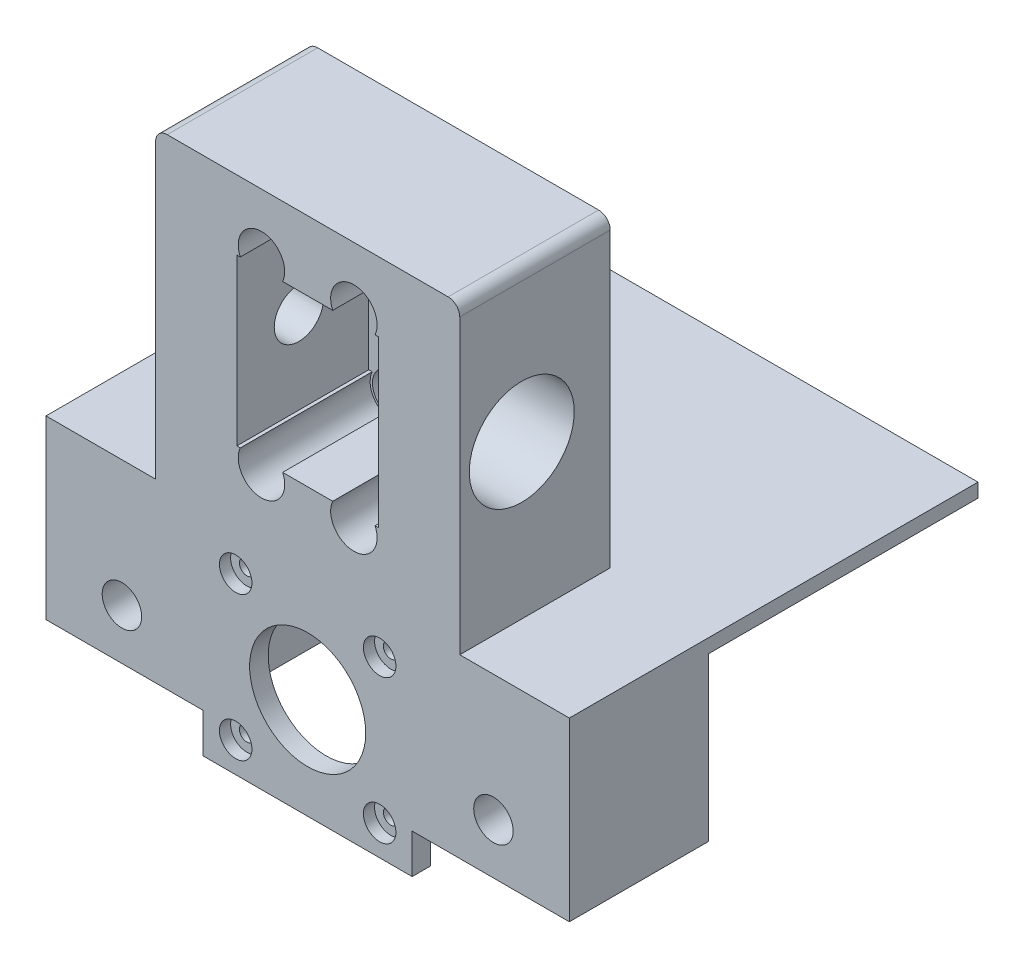
SolidWorks part; units mm, degrees
ref_plane "Front Plane" through (0, 0, 0) normal (0, 0, 1) x (1, 0, 0)
ref_plane "Top Plane" through (0, 0, 0) normal (0, 1, 0) x (1, 0, 0)
ref_plane "Right Plane" through (0, 0, 0) normal (1, 0, 0) x (0, 0, -1)
sketch "Sketch1" plane through (0, 0, 0) normal (0, 0, 1) x (1, 0, 0)
  line L1 (0, 0) -> (-65.5, 0)
  line L2 (0, 0) -> (0, -65.5)
  line L3 (0, -65.5) -> (-65.5, -65.5)
  line L4 (-65.5, 0) -> (-65.5, -65.5)
  line L5 (-17.5, -14.95) -> (-48, -14.95)
  line L6 (-17.5, -14.95) -> (-17.5, -50.55)
  line L7 (-17.5, -50.55) -> (-48, -50.55)
  line L8 (-48, -14.95) -> (-48, -50.55)
  point P10 (-32.75, -14.95)
  point P11 (-48, -32.75)
  point P12 (-65.5, -32.75)
  point P13 (-32.75, 0)
  dimension "D1" = 65.5
  dimension "D2" = 35.6
  dimension "D3" = 30.5
extrude "Boss-Extrude1" add sketch "Sketch1" along normal blind 28.4 and the other way blind 4
sketch "Sketch5" plane through (0, 0, 0) normal (1, 0, 0) x (0, 0, -1)
  line L2 (4, -65.5) -> (4, 0) construction
  line L4 (4, 0) -> (-28.4, 0) construction
  circle A1 centre (-15.05, -32.45) radius 11.3
  dimension "D1" = 11.3
  dimension "D2" = 19.05
  dimension "D3" = 32.45
extrude "Cut-Extrude1" cut sketch "Sketch5" against normal up to next
sketch "Sketch7" plane through (-65.5, 0, 0) normal (1, 0, 0) x (0, 0, -1)
  circle A1 centre (-15.05, -32.45) radius 5.3
  circle A3 centre (-15.05, -32.45) radius 11.3 construction
  circle A4 centre (-15.05, -32.45) radius 11.3 construction
  dimension "D1" = 5.3
extrude "Cut-Extrude4" cut sketch "Sketch7" along normal up to next
sketch "Sketch8" plane through (0, 0, -4) normal (0, 0, -1) x (-1, 0, 0)
  line L4 (17.5, -14.95) -> (17.5, -50.55)
  line L5 (48, -14.95) -> (17.5, -14.95)
  line L6 (48, -50.55) -> (48, -14.95)
  line L7 (17.5, -50.55) -> (48, -50.55)
  line L8 (17.5, -14.95) -> (17.5, -50.55)
  line L9 (48, -14.95) -> (17.5, -14.95)
  line L10 (48, -50.55) -> (48, -14.95)
  line L11 (17.5, -50.55) -> (48, -50.55)
  dimension "D2" = 30.5
  dimension "D3" = 35.6
  dimension "D1" = 0
extrude "Boss-Extrude2" add sketch "Sketch8" against normal blind 4
sketch "Sketch9" plane through (0, 0, -4) normal (0, 0, 1) x (1, 0, 0)
  line L0 (0, 0) -> (-65.5, 0) construction
  line L1 (0, 0) -> (0, -65.5) construction
  line L2 (0, -65.5) -> (-65.5, -65.5) construction
  line L3 (-32.75, -65.5) -> (-32.75, 0) construction
  line L4 (0, -32.75) -> (-65.5, -32.75) construction
  line L5 (-65.5, 0) -> (-65.5, -65.5) construction
  line L6 (-32.75, -65.5) -> (-32.75, -53.5) construction
  line L7 (-65.5, -65.5) -> (0, 0) construction
  circle A0 centre (-12.75, -12.9) radius 4.9
  circle A1 centre (-52.75, -12.9) radius 4.9
  circle A2 centre (-52.75, -52.6) radius 4.9
  circle A3 centre (-12.75, -52.6) radius 4.9
  point P20 (-32.75, -12)
  point P26 (-12, -32.75)
  point P27 (-53.5, -32.75)
  dimension "D3" = 9.8
  dimension "D1" = 12.9
  dimension "D2" = 12.75
  dimension "D4" = 12
extrude "Cut-Extrude5" cut sketch "Sketch9" along normal blind 2.2
fillet "Fillet1" radius 2.5 2 edges at (0, 0, 12.2) (-65.5, 0, 12.2)
sketch "Sketch10" plane through (0, 0, 0) normal (0, 0, 1) x (1, 0, 0)
  line L0 (0, -52.6) -> (-22.8, -52.6) construction
  line L1 (0, 0) -> (0, -65.5) construction
  line L2 (-22.8, -52.6) -> (-22.8, -65.5) construction
  line L3 (0, -65.5) -> (-65.5, -65.5) construction
  line L5 (-32.75, -65.5) -> (-32.75, 0) construction
  line L6 (0, -32.75) -> (-65.5, -32.75) construction
  line L7 (-32.75, -65.5) -> (-32.75, 0) construction
  line L8 (0, -32.75) -> (-65.5, -32.75) construction
  circle A0 centre (-22.8, -12.9) radius 5
  circle A1 centre (-42.7, -12.9) radius 5
  circle A2 centre (-22.8, -52.6) radius 5
  circle A3 centre (-42.7, -52.6) radius 5
  point P7 (-22.8, -12.9)
  point P8 (-42.7, -12.9)
  point P13 (-42.7, -52.6)
  dimension "D3" = 10
  dimension "D1" = 22.8
  dimension "D2" = 12.9
extrude "Cut-Extrude7" cut sketch "Sketch10" along normal up to next
sketch "Sketch20" plane through (0, 0, 0) normal (0, 0, 1) x (1, 0, 0)
  line L0 (-32.75, 0) -> (-32.75, -65.5) construction
  line L1 (-32.75, -65.5) -> (-32.75, 0) construction
  line L2 (-65.5, -32.75) -> (0, -32.75) construction
  line L3 (0, -32.75) -> (-65.5, -32.75) construction
  line L4 (-62.12, -65.5) -> (-3.38, -65.5) construction
  line L5 (0, -65.5) -> (-65.5, -65.5) construction
  line L6 (0, 0) -> (-65.5, 0) construction
  line L7 (0, 0) -> (0, -65.5) construction
  line L8 (-65.5, 0) -> (-65.5, -65.5) construction
  arc A0 (-38.1396, -14.95) -> (-47.2604, -14.95) centre (-42.7, -12.9) ccw construction
  point P0 (-42.7, -12.9)
  point P13 (-22.8, -12.9)
  point P15 (-22.8, -52.6)
  point P16 (-42.7, -52.6)
hole_wizard "CBORE for M4 Pan Head Machine Screw1" positions "3DSketch5" profile "Sketch22" counterbore size "M4" standard "ANSI Metric"
sketch3d "3DSketch5"
  point P0 (-42.7, -12.9, 0)
  point P3 (-22.8, -12.9, 0)
  point P6 (-42.7, -52.6, 0)
  point P9 (-22.8, -52.6, 0)
sketch "Sketch22" plane through (-42.7, -12.9, 0) normal (1, 0, 0) x (0, -1, 0)
  line L0 (0, 0) -> (0, 9.4421)
  line L1 (0, 9.4421) -> (2.4, 8)
  line L2 (2.4, 8) -> (2.4, 3.1)
  line L3 (2.4, 3.1) -> (4.5, 3.1)
  line L4 (4.5, 3.1) -> (4.5, 0)
  line L5 (4.5, 0) -> (0, 0)
  line L10 (0, 9.4421) -> (-2.4, 8) construction
  line L11 (0, -6.35) -> (0, 107.95) construction
  dimension "Hole Dia." = 4.8
  dimension "Hole Depth" = 8
  dimension "C'Bore Dia." = 9
  dimension "C'Bore Depth" = 3.1
  dimension "Drill Angle" = 118
sketch "Sketch23" plane through (0, -65.5, 0) normal (0, -1, 0) x (1, 0, 0)
  line L1 (23.6, 28.4) -> (-89.1, 28.4)
  line L2 (23.6, 28.4) -> (23.6, -59.6)
  line L3 (23.6, -59.6) -> (-89.1, -59.6)
  line L4 (-89.1, 28.4) -> (-89.1, -59.6)
  line L9 (-65.5, 28.4) -> (0, 28.4) construction
  point P4 (-32.75, -59.6)
  dimension "D1" = 88
  dimension "D2" = 112.7
extrude "Boss-Extrude3" add sketch "Sketch23" along normal blind 3
sketch "Sketch24" plane through (0, -68.5, 0) normal (0, -1, 0) x (-1, 0, 0)
  line L0 (-23.6, -28.4) -> (89.1, -28.4) construction
  line L1 (55.25, -28.4) -> (10.25, -28.4)
  line L2 (55.25, -28.4) -> (55.25, -24.4)
  line L3 (55.25, -24.4) -> (10.25, -24.4)
  line L4 (10.25, -28.4) -> (10.25, -24.4)
  point P6 (32.75, -28.4)
  dimension "D1" = 4
  dimension "D2" = 45
extrude "Boss-Extrude4" add sketch "Sketch24" along normal blind 43.5
sketch "Sketch25" plane through (0, 0, 28.4) normal (0, 0, 1) x (1, 0, 0)
  line L1 (-55.25, -68.5) -> (-89.1, -68.5) construction
  line L2 (-32.75, -112) -> (-32.75, 0) construction
  line L3 (-10.25, -112) -> (-55.25, -112) construction
  line L4 (-2.5, 0) -> (-63, 0) construction
  point P0 (-48.25, -74.5)
  point P5 (-48.25, -105.5)
  dimension "D1" = 15.5
  dimension "D2" = 6
  dimension "D3" = 31
sketch "Sketch28" plane through (0, 0, 28.4) normal (0, 0, 1) x (1, 0, 0)
  line L0 (-10.25, -112) -> (-55.25, -68.5) construction
  circle A0 centre (-32.75, -90.25) radius 22.0978
  circle A1 centre (-32.75, -90.25) radius 12.5
  dimension "D1" = 25
hole_wizard "CBORE for M3 Pan Head Machine Screw1" positions "Sketch26" profile "Sketch27" counterbore size "M3" standard "ANSI Metric" end condition up to next
sketch "Sketch26" plane through (0, 0, 28.4) normal (0, 0, 1) x (1, 0, 0)
  point P0 (-48.25, -74.5)
  point P4 (-48.25, -105.5)
sketch "Sketch27" plane through (-48.25, -74.5, 28.4) normal (1, 0, 0) x (0, -1, 0)
  line L0 (0, 0) -> (0, 4)
  line L1 (0, 4) -> (1.6, 4)
  line L3 (1.6, 4) -> (1.6, 2.4)
  line L4 (1.6, 2.4) -> (3.5, 2.4)
  line L5 (3.5, 2.4) -> (3.5, 0)
  line L7 (3.5, 0) -> (0, 0)
  line L11 (0, -6.35) -> (0, 107.95) construction
  dimension "Thru Hole Dia." = 3.2
  dimension "Thru Hole Depth" = 4
  dimension "C'Bore Dia." = 7
  dimension "C'Bore Depth" = 2.4
ref_plane "Plane1" through (-32.75, 0, 0) normal (1, 0, 0) x (0, 0, -1)
extrude "Cut-Extrude8" cut sketch "Sketch28" against normal up to next contours A1
mirror "Mirror1" about plane through (-32.75, 0, 0) normal (1, 0, 0) of "CBORE for M3 Pan Head Machine Screw1"
sketch "Sketch29" plane through (0, 0, 28.4) normal (0, 0, 1) x (1, 0, 0)
  line L0 (-32.75, -89.65) -> (-55.25, -89.65) construction
  line L1 (-55.25, -112) -> (-55.25, -68.5) construction
sketch "Sketch30" plane through (0, -68.5, 0) normal (0, -1, 0) x (-1, 0, 0)
  line L1 (55.25, -28.4) -> (89.1, -28.4)
  line L2 (55.25, -28.4) -> (55.25, 1.6)
  line L3 (55.25, 1.6) -> (89.1, 1.6)
  line L4 (89.1, -28.4) -> (89.1, 1.6)
  line L5 (89.1, -28.4) -> (89.1, 59.6) construction
  dimension "D1" = 30
extrude "Boss-Extrude5" add sketch "Sketch30" along normal blind 35
sketch "Sketch31" plane through (0, 0, 28.4) normal (0, 0, 1) x (1, 0, 0)
  line L0 (-72.75, -92.65) -> (-72.75, -103.5) construction
  line L1 (-55.25, -103.5) -> (-89.1, -103.5) construction
  circle A0 centre (-72.75, -92.65) radius 4.25
  dimension "D3" = 8.5
  dimension "D1" = 3
  dimension "D2" = 40
sketch "Sketch33" plane through (0, -103.5, 0) normal (0, -1, 0) x (-1, 0, 0)
  line L0 (72.75, -28.4) -> (72.75, 1.6) construction
  line L1 (89.1, 1.6) -> (55.25, 1.6) construction
  point P5 (72.75, -13.4)
  point P6 (72.75, -21.4)
  point P7 (72.75, -5.4)
  dimension "D1" = 8
  dimension "D2" = 8
extrude "Cut-Extrude10" cut sketch "Sketch31" against normal up to next
hole_wizard "CBORE for M3 Pan Head Machine Screw2" positions "Sketch34" profile "Sketch35" counterbore size "M3" standard "ANSI Metric" end condition up to next
sketch "Sketch34" plane through (0, -103.5, 0) normal (0, -1, 0) x (-1, 0, 0)
  point P0 (72.75, -13.4)
sketch "Sketch35" plane through (-72.75, -103.5, 13.4) normal (1, 0, 0) x (0, 0, -1)
  line L0 (0, 0) -> (0, 6.6)
  line L1 (0, 6.6) -> (1.6, 6.6)
  line L3 (1.6, 6.6) -> (1.6, 2.4)
  line L4 (1.6, 2.4) -> (3.5, 2.4)
  line L5 (3.5, 2.4) -> (3.5, 0)
  line L7 (3.5, 0) -> (0, 0)
  line L11 (0, -6.35) -> (0, 107.95) construction
  dimension "Thru Hole Dia." = 3.2
  dimension "Thru Hole Depth" = 6.6
  dimension "C'Bore Dia." = 7
  dimension "C'Bore Depth" = 2.4
mirror "Mirror2" about plane through (-32.75, 0, 0) normal (1, 0, 0) of "Cut-Extrude10", "CBORE for M3 Pan Head Machine Screw2", "Boss-Extrude5"
